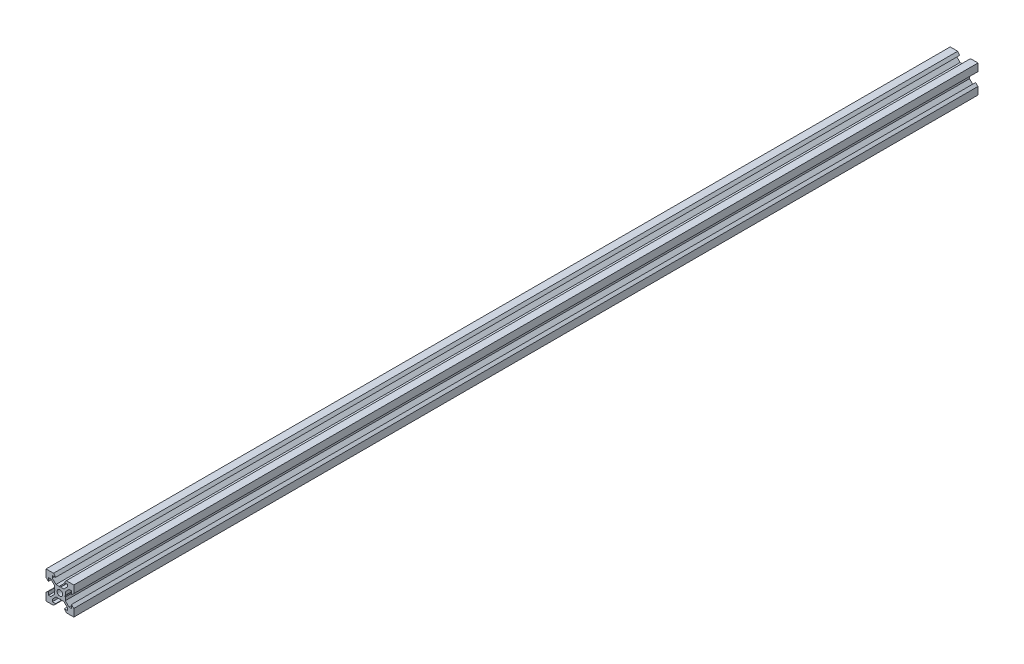
SolidWorks part; units mm, degrees
ref_plane "Front Plane" through (0, 0, 0) normal (0, 0, 1) x (1, 0, 0)
ref_plane "Top Plane" through (0, 0, 0) normal (0, 1, 0) x (1, 0, 0)
ref_plane "Right Plane" through (0, 0, 0) normal (1, 0, 0) x (0, 0, -1)
sketch "Sketch1" plane through (0, 0, 0) normal (0, 0, 1) x (1, 0, 0)
  line L0 (10, 10) -> (4.6104, 10) construction
  line L1 (10, 10) -> (10, 4.6104) construction
  line L2 (10, -10) -> (10, -4.6104) construction
  line L3 (10, -10) -> (4.6104, -10) construction
  line L4 (10, 10) -> (10, 4.6104)
  line L5 (6.5607, 5.5) -> (8.2, 5.5)
  line L6 (5.5, 8.2) -> (5.5, 6.5607)
  line L7 (10, 10) -> (4.6104, 10)
  line L8 (10, 10) -> (10, 4.6104)
  line L9 (6.5607, 5.5) -> (3.9, 2.8393)
  line L10 (5.5, 6.5607) -> (2.8393, 3.9)
  line L11 (10, 4.6104) -> (8.2, 3.1)
  line L12 (4.6104, 10) -> (3.1, 8.2)
  line L13 (8.2, 3.1) -> (8.2, 5.5)
  line L14 (3.1, 8.2) -> (5.5, 8.2)
  line L15 (-6.5607, 5.5) -> (-8.2, 5.5)
  line L16 (6.5607, -5.5) -> (8.2, -5.5)
  line L17 (3.1, -8.2) -> (5.5, -8.2)
  line L18 (8.2, -3.1) -> (8.2, -5.5)
  line L19 (4.6104, -10) -> (3.1, -8.2)
  line L20 (10, -4.6104) -> (8.2, -3.1)
  line L21 (0.5196, -3.9) -> (0, -3.6)
  line L22 (0.5196, 3.9) -> (0, 3.6)
  line L23 (3.6, 0) -> (3.9, -0.5196)
  line L24 (3.9, 0.5196) -> (3.6, 0)
  line L25 (3.9, 0.5196) -> (3.9, 2.8393)
  line L26 (2.8393, 3.9) -> (0.5196, 3.9)
  line L27 (3.9, -2.8393) -> (3.9, -0.5196)
  line L28 (2.8393, -3.9) -> (0.5196, -3.9)
  line L29 (5.5, -6.5607) -> (2.8393, -3.9)
  line L30 (6.5607, -5.5) -> (3.9, -2.8393)
  line L31 (10, -10) -> (10, -4.6104)
  line L32 (10, -10) -> (4.6104, -10)
  line L33 (5.5, -8.2) -> (5.5, -6.5607)
  line L34 (-6.5607, -5.5) -> (-8.2, -5.5)
  line L35 (10, -10) -> (10, -4.6104)
  line L36 (0, 0) -> (0, 8.2) construction
  line L37 (-10, -10) -> (-4.6104, -10) construction
  line L38 (-10, -10) -> (-10, -4.6104) construction
  line L39 (-10, 10) -> (-10, 4.6104) construction
  line L40 (-10, 10) -> (-4.6104, 10) construction
  line L41 (-10, -10) -> (-10, -4.6104)
  line L43 (-5.5, -8.2) -> (-5.5, -6.5607)
  line L44 (-10, -10) -> (-4.6104, -10)
  line L45 (-10, -10) -> (-10, -4.6104)
  line L46 (-6.5607, -5.5) -> (-3.9, -2.8393)
  line L47 (-5.5, -6.5607) -> (-2.8393, -3.9)
  line L48 (-2.8393, -3.9) -> (-0.5196, -3.9)
  line L49 (-3.9, -2.8393) -> (-3.9, -0.5196)
  line L50 (-2.8393, 3.9) -> (-0.5196, 3.9)
  line L51 (-3.9, 0.5196) -> (-3.9, 2.8393)
  line L52 (-3.9, 0.5196) -> (-3.6, 0)
  line L53 (-3.6, 0) -> (-3.9, -0.5196)
  line L54 (-0.5196, 3.9) -> (0, 3.6)
  line L55 (-0.5196, -3.9) -> (0, -3.6)
  line L56 (-10, -4.6104) -> (-8.2, -3.1)
  line L57 (-4.6104, -10) -> (-3.1, -8.2)
  line L58 (-8.2, -3.1) -> (-8.2, -5.5)
  line L59 (-3.1, -8.2) -> (-5.5, -8.2)
  line L60 (-10, -10) -> (10, -10) construction
  line L61 (-10, -10) -> (-10, 10) construction
  line L62 (-3.1, 8.2) -> (-5.5, 8.2)
  line L63 (-8.2, 3.1) -> (-8.2, 5.5)
  line L64 (-4.6104, 10) -> (-3.1, 8.2)
  line L65 (-10, 4.6104) -> (-8.2, 3.1)
  line L66 (-5.5, 6.5607) -> (-2.8393, 3.9)
  line L67 (-6.5607, 5.5) -> (-3.9, 2.8393)
  line L68 (-10, 10) -> (-10, 4.6104)
  line L69 (-10, 10) -> (-4.6104, 10)
  line L70 (-5.5, 8.2) -> (-5.5, 6.5607)
  line L71 (-10, 10) -> (10, 10) construction
  line L72 (-10, 10) -> (-10, 4.6104)
  line L73 (10, -10) -> (10, 10) construction
  line L74 (-10, -10) -> (10, 10) construction
  line L75 (-10, 10) -> (10, -10) construction
  circle A0 centre (0, 0) radius 2
  dimension "D7" = 4
  dimension "D1" = 20
  dimension "D2" = 5.3896
  dimension "D3" = 4.5
  dimension "D4" = 50
  dimension "D5" = 1.8
  dimension "D6" = 1.5104
  dimension "D8" = 5.5
  dimension "D9" = 120
  dimension "D10" = 0.3
  dimension "D11" = 2.3197
  dimension "D12" = 7.8
  dimension "D13" = 7.8
  dimension "D14" = 1.5
  dimension "D15" = 2.6607
extrude "Boss-Extrude1" add sketch "Sketch1" along normal mid plane 650 contours L70 L62 L64 L69 L68 L65 L63 L15 L67 L51 L52 L53 L49 L46 L34 L58 L56 L41 L44 L57 L59 L43 L47 L48 L55 L21 L28 L29 L33 L17 L19 L32 L31 L20 L18 L16 L30 L27 L23 L24 L25 L9 L5 L13 L11 L4 L7 L12 L14 L6 L10 region at (9.7172, 7.3052, 0)
